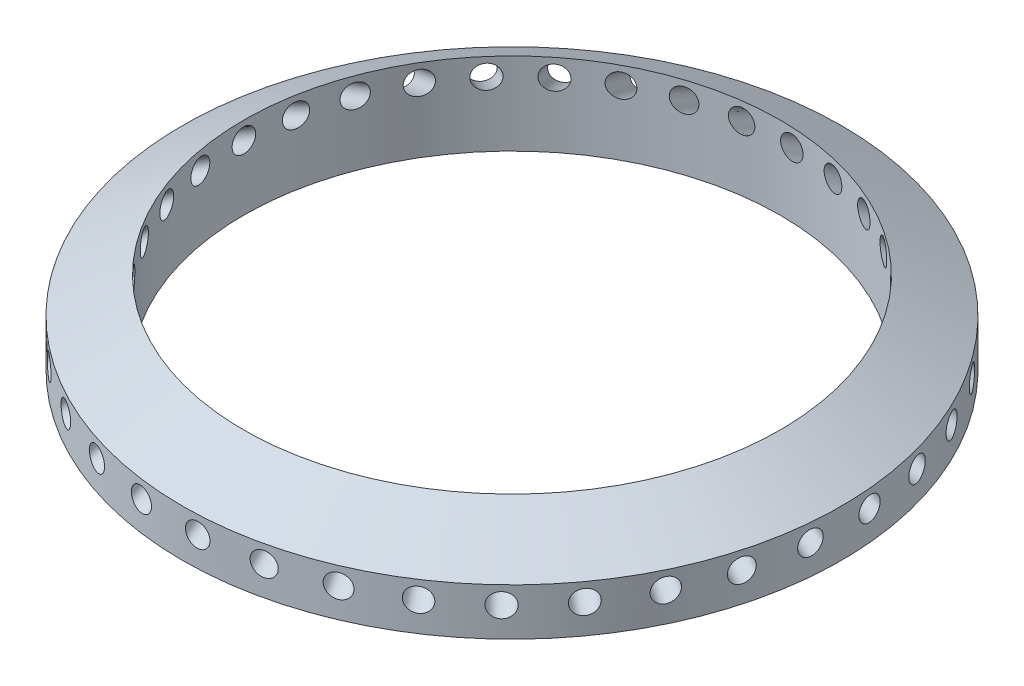
SolidWorks part; units mm, degrees
material "ABS"
ref_plane "Alzado" through (0, 0, 0) normal (0, 0, 1) x (1, 0, 0)
ref_plane "Planta" through (0, 0, 0) normal (0, 1, 0) x (1, 0, 0)
ref_plane "Vista lateral" through (0, 0, 0) normal (1, 0, 0) x (0, 0, -1)
sketch "Croquis1" plane through (0, 0, 0) normal (0, 0, 1) x (1, 0, 0)
  line L0 (0, 0) -> (-22.8, 0) construction
  line L1 (-22.8, 0) -> (-28, 0)
  line L2 (-28, 0) -> (-28, 1)
  line L3 (-28, 1) -> (-28, 4)
  line L4 (-22.8, 0) -> (-22.8, 7.0022)
  line L5 (-22.8, 7.0022) -> (-28, 4)
  line L6 (0, 0) -> (0, 7.1054) construction
  dimension "D1" = 22.8
  dimension "D2" = 28
  dimension "D3" = 1
  dimension "D4" = 3
  dimension "D5" = 30
revolve "Revolución1" add sketch "Croquis1" angle 360 about L6
ref_plane "Plano1" through (-28, 0, 0) normal (-1, 0, 0) x (0, 0, 1)
sketch "Croquis2" plane through (-28, 0, 0) normal (-1, 0, 0) x (0, 0, 1)
  line L0 (0, 1) -> (0, 4) construction
  circle A0 centre (0, 2.5) radius 1
  dimension "D1" = 2
extrude "Cortar-Extruir1" cut sketch "Croquis2" along direction (-0.866, -0.5, 0) on the side against the normal blind 10
pattern_circular "MatrizC1" count 35 over 360 about axis through (0, 0, 0) along (0, -1, 0) of "Cortar-Extruir1"
sketch "Croquis3" plane through (0, 0, 0) normal (0, -1, 0) x (1, 0, 0)
  line L0 (-22.8, 0) -> (-22.3759, 4.3773) construction
  line L1 (-27.8695, 2.7004) -> (-26.8741, 2.6039) construction
  line L2 (-22.5879, 2.1886) -> (-27.8695, 2.7004) construction
  circle A0 centre (0, 0) radius 22.8 construction
  circle A1 centre (0, 0) radius 28 construction
  circle A2 centre (-25.0825, 2.4303) radius 1.8
  circle A3 centre (2.4303, 25.0825) radius 1.8
  circle A4 centre (25.0825, -2.4303) radius 1.8
  circle A5 centre (-2.4303, -25.0825) radius 1.8
  point P22 (0, 0)
  dimension "D1" = 1
  dimension "D2" = 3.6
  dimension "D3" = 4
extrude "Cortar-Extruir2" cut sketch "Croquis3" against normal blind 3.5
